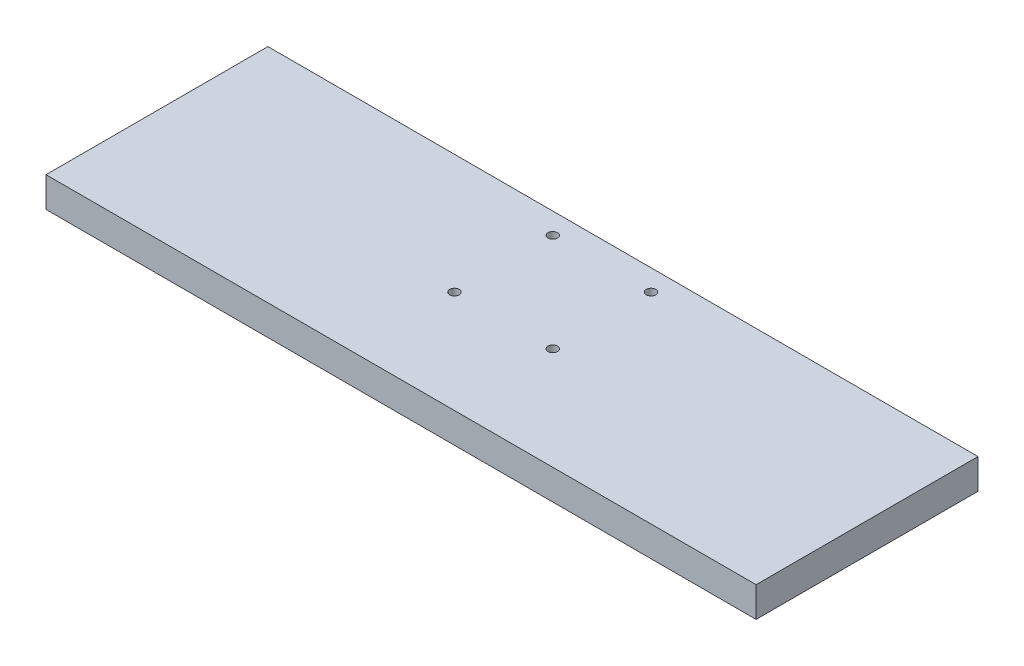
SolidWorks part; units mm, degrees
ref_plane "前视基准面" through (0, 0, 0) normal (0, 0, 1) x (1, 0, 0)
ref_plane "上视基准面" through (0, 0, 0) normal (0, 1, 0) x (1, 0, 0)
ref_plane "右视基准面" through (0, 0, 0) normal (1, 0, 0) x (0, 0, -1)
sketch "草图2" plane through (0, 0, 0) normal (0, 1, 0) x (1, 0, 0)
  line L1 (112, 35) -> (-112, 35)
  line L2 (112, 35) -> (112, -35)
  line L3 (112, -35) -> (-112, -35)
  line L4 (-112, 35) -> (-112, -35)
  line L5 (112, 35) -> (-112, -35) construction
  line L6 (112, -35) -> (-112, 35) construction
  point P0 (0, 0)
  dimension "D1" = 70
  dimension "D2" = 224
extrude "凸台-拉伸1" add sketch "草图2" along normal blind 9.5
sketch "草图3" plane through (0, 9.5, 0) normal (0, 1, 0) x (1, 0, 0)
  line L0 (0, 35) -> (0, -35) construction
  line L1 (112, 35) -> (-112, 35) construction
  line L2 (-112, -35) -> (112, -35) construction
sketch "草图4" plane through (0, 9.5, 0) normal (0, 1, 0) x (1, 0, 0)
  circle A0 centre (15.5, -2.65) radius 1.5
  circle A1 centre (-15.5, -2.65) radius 1.5
  circle A2 centre (15.5, 28.35) radius 1.5
  circle A3 centre (-15.5, 28.35) radius 1.5
  dimension "D1" = 3
extrude "切除-拉伸1" cut sketch "草图4" against normal through all
